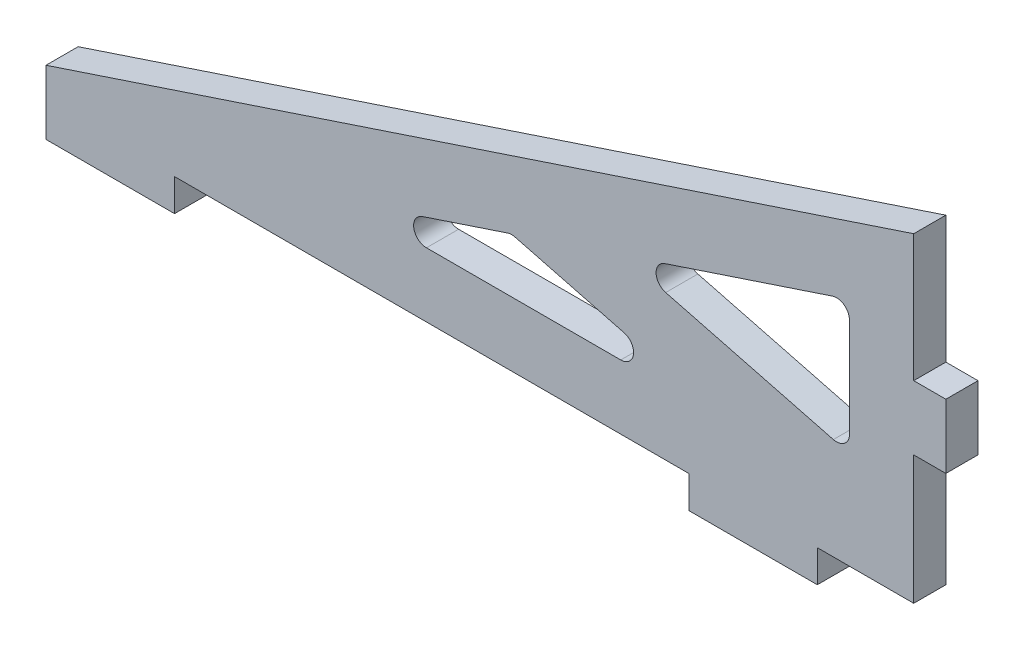
SolidWorks part; units mm, degrees
ref_plane "Front Plane" through (0, 0, 0) normal (0, 0, 1) x (1, 0, 0)
ref_plane "Top Plane" through (0, 0, 0) normal (0, 1, 0) x (1, 0, 0)
ref_plane "Right Plane" through (0, 0, 0) normal (1, 0, 0) x (0, 0, -1)
sketch "Sketch2" plane through (0, 0, 0) normal (0, 0, 1) x (1, 0, 0)
  line L0 (-92.95, 148.308) -> (78.5, 205.204)
  line L1 (78.5, 205.204) -> (84.85, 205.204) construction
  line L2 (84.85, 205.204) -> (84.85, 180.058) construction
  line L4 (-118.35, 135.608) -> (-118.35, 141.958) construction
  line L5 (84.85, 167.358) -> (84.85, 141.958) construction
  line L6 (84.85, 180.058) -> (78.5, 180.058)
  line L8 (84.85, 167.358) -> (78.5, 167.358)
  line L9 (78.5, 180.058) -> (78.5, 167.358) construction
  line L10 (-92.95, 135.608) -> (-92.95, 148.308) construction
  line L13 (-67.55, 141.958) -> (-67.55, 135.608)
  line L15 (34.05, 135.608) -> (34.05, 141.958)
  line L17 (59.45, 141.958) -> (59.45, 135.608)
  line L19 (-92.95, 135.608) -> (-118.35, 135.608) construction
  line L20 (-92.95, 141.958) -> (-92.95, 135.608)
  line L21 (-92.95, 141.958) -> (-92.95, 148.308)
  line L22 (-92.95, 135.608) -> (-67.55, 135.608)
  line L23 (-67.55, 141.958) -> (34.05, 141.958)
  line L24 (34.05, 135.608) -> (59.45, 135.608)
  line L25 (59.45, 141.958) -> (78.5, 141.958)
  line L26 (78.5, 167.358) -> (78.5, 141.958)
  line L27 (84.85, 167.358) -> (84.85, 180.058)
  line L28 (78.5, 180.058) -> (78.5, 205.204)
  dimension "D1" = 6.35
  dimension "D2" = 6.35
  dimension "D3" = 6.35
  dimension "D4" = 12.7
  dimension "D5" = 6.35
  dimension "D6" = 25.4
  dimension "D7" = 25.4
  dimension "D8" = 25.4
  dimension "D9" = 25.4
  dimension "D10" = 6.35
  dimension "D11" = 25.4
extrude "Boss-Extrude1" add sketch "Sketch2" along normal blind 6.35
sketch "Sketch3" plane through (0, 0, 6.35) normal (0, 0, 1) x (1, 0, 0)
  line L0 (-33.4926, 154.658) -> (65.8, 187.6084)
  line L1 (65.8, 187.6084) -> (65.8, 154.658)
  line L2 (65.8, 154.658) -> (-33.4926, 154.658)
  line L3 (78.5, 205.204) -> (-92.95, 148.308) construction
  line L4 (-67.55, 141.958) -> (34.05, 141.958) construction
  line L6 (65.8, 154.658) -> (-19.3713, 176.756) construction
  line L7 (64.2053, 148.5115) -> (-20.9661, 170.6095)
  line L8 (67.3947, 160.8045) -> (-17.7766, 182.9025)
  line L9 (78.5, 180.058) -> (78.5, 205.204) construction
  arc A0 (64.2053, 148.5115) -> (67.3947, 160.8045) centre (65.8, 154.658) ccw
  arc A1 (-17.7766, 182.9025) -> (-20.9661, 170.6095) centre (-19.3713, 176.756) ccw
  point P10 (23.2143, 165.707)
  dimension "D4" = 6.35
  dimension "D1" = 12.7
  dimension "D2" = 12.7
  dimension "D3" = 12.7
extrude "Cut-Extrude1" cut sketch "Sketch3" against normal through all contours L2 L7 L0 | L8 L1 L0 region at (2.001, 158.2501, 6.35) region at (50.9232, 173.8748, 6.35)
fillet "Fillet1" radius 2.54 6 edges at (65.8, 187.6084, 3.175) (21.1696, 172.7978, 3.175) (-1.0194, 165.4343, 3.175) (40.5151, 154.658, 3.175) (-33.4926, 154.658, 3.175) (65.8, 161.2182, 3.175)
